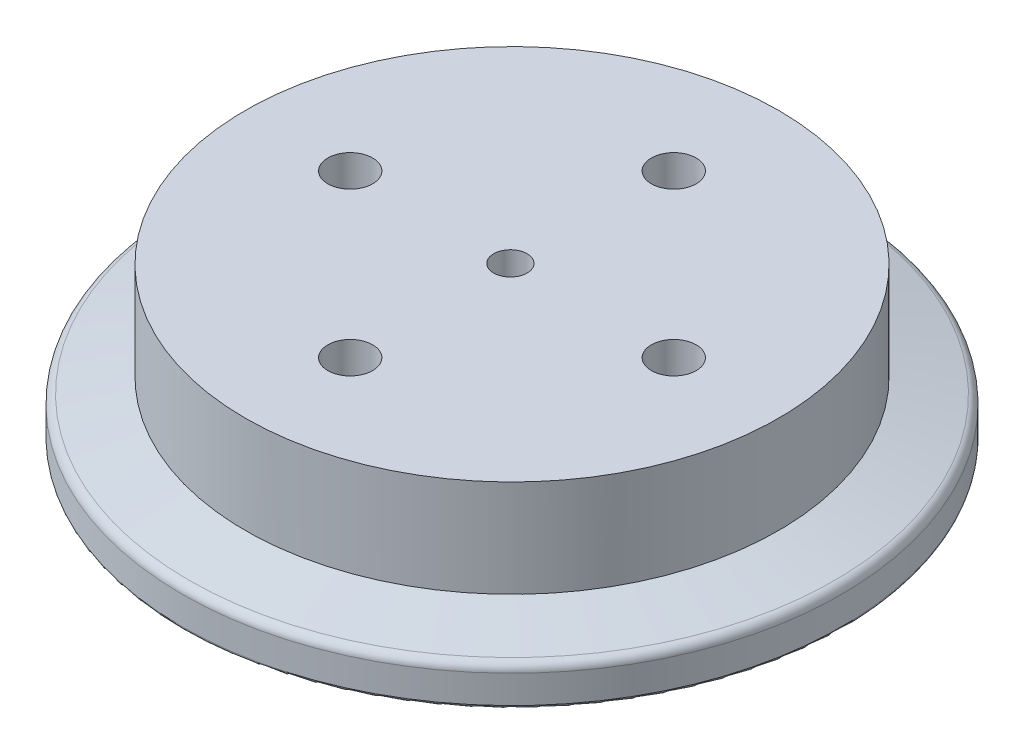
SolidWorks part; units mm, degrees
material "AISI 304"
ref_plane "Front Plane" through (0, 0, 0) normal (0, 0, 1) x (1, 0, 0)
ref_plane "Top Plane" through (0, 0, 0) normal (0, 1, 0) x (1, 0, 0)
ref_plane "Right Plane" through (0, 0, 0) normal (1, 0, 0) x (0, 0, -1)
sketch "Sketch1" plane through (0, 0, 0) normal (1, 0, 0) x (0, 0, -1)
  line L0 (0, 0) -> (0, 5.1) construction
  line L1 (-27.5, 0) -> (-27.5, 3.175)
  line L2 (-27.5, 3.175) -> (-20.3158, 5.1)
  line L6 (0, 2.5) -> (-20.625, 2.5)
  line L7 (-20.625, 2.5) -> (-20.625, 0)
  line L8 (-20.625, 0) -> (-27.5, 0)
  line L9 (-20.3158, 5.1) -> (0, 5.1)
  line L10 (0, 5.1) -> (0, 2.5)
  dimension "D1" = 75
  dimension "D2" = 40.6316
  dimension "Flange ID" = 41.25
  dimension "Flange OD" = 55
  dimension "D5" = 3.175
  dimension "Flange Height" = 5.1
  dimension "D9" = 2.5
revolve "Flange" add sketch "Sketch1" angle 360 about L0
sketch "Sketch2" plane through (0, 0, 0) normal (1, 0, 0) x (0, 0, -1)
  line L0 (0, 2.5) -> (-20.625, 2.5) construction
  line L1 (0, 0) -> (-15.85, 0)
  line L2 (0, 0) -> (0, 2.5)
  line L3 (0, 2.5) -> (-15.85, 2.5)
  line L4 (-15.85, 0) -> (-15.85, 2.5)
  line L5 (0, 0) -> (0, -4.8376) construction
  dimension "ID" = 31.7
revolve "Blank Insert" add sketch "Sketch2" angle 360 about L5
sketch "Sketch5" plane through (0, 2.5, 0) normal (0, -1, 0) x (1, 0, 0)
  circle A0 centre (0, 0) radius 22.25
  dimension "D1" = 44.5
extrude "Stub" add sketch "Sketch5" against normal offset from surface (10.2 mm away) 12.7 up to face at (0, 0, -20.625)
ref_plane "Plane1" through (0, -1.905, 0) normal (0, -1, 0) x (-1, 0, 0)
ref_plane "Plane2" through (0, 2.5, 0) normal (0, -1, 0) x (-1, 0, 0)
ref_plane "Plane3" through (0, 5.1, 0) normal (0, -1, 0) x (-1, 0, 0)
fillet "Fillet1" radius 0.762 1 edges at (0, 3.175, -27.5)
fillet "Fillet2" radius 0.254 1 edges at (0, 0, -27.5)
sketch "Sketch7" plane through (0, 12.7, 0) normal (0, 1, 0) x (1, 0, 0)
  line L0 (0, 22.25) -> (0, -22.25) construction
  line L1 (22.25, 0) -> (-22.25, 0) construction
  line L2 (0, 0) -> (0, 13.5) construction
  circle A0 centre (0, 0) radius 22.25 construction
  circle A1 centre (0, 0) radius 22.25 construction
  circle A2 centre (0, 13.5) radius 1.87
  circle A3 centre (13.5, 0) radius 1.87
  circle A4 centre (0, -13.5) radius 1.87
  circle A5 centre (-13.5, 0) radius 1.87
  dimension "D1" = 4
  dimension "D2" = 13.5
extrude "Cut-Extrude1" cut sketch "Sketch7" against normal blind 3.175
sketch "Sketch8" plane through (0, 12.7, 0) normal (0, 1, 0) x (1, 0, 0)
  line L0 (-0.1333, -22.2496) -> (-0.1333, 22.2496) construction
  line L1 (-22.25, 0) -> (22.25, 0) construction
  circle A0 centre (-0.1333, 0) radius 1.397
  circle A1 centre (0, 0) radius 22.25 construction
  circle A2 centre (0, 0) radius 22.25 construction
extrude "Cut-Extrude2" cut sketch "Sketch8" against normal blind 304.8
